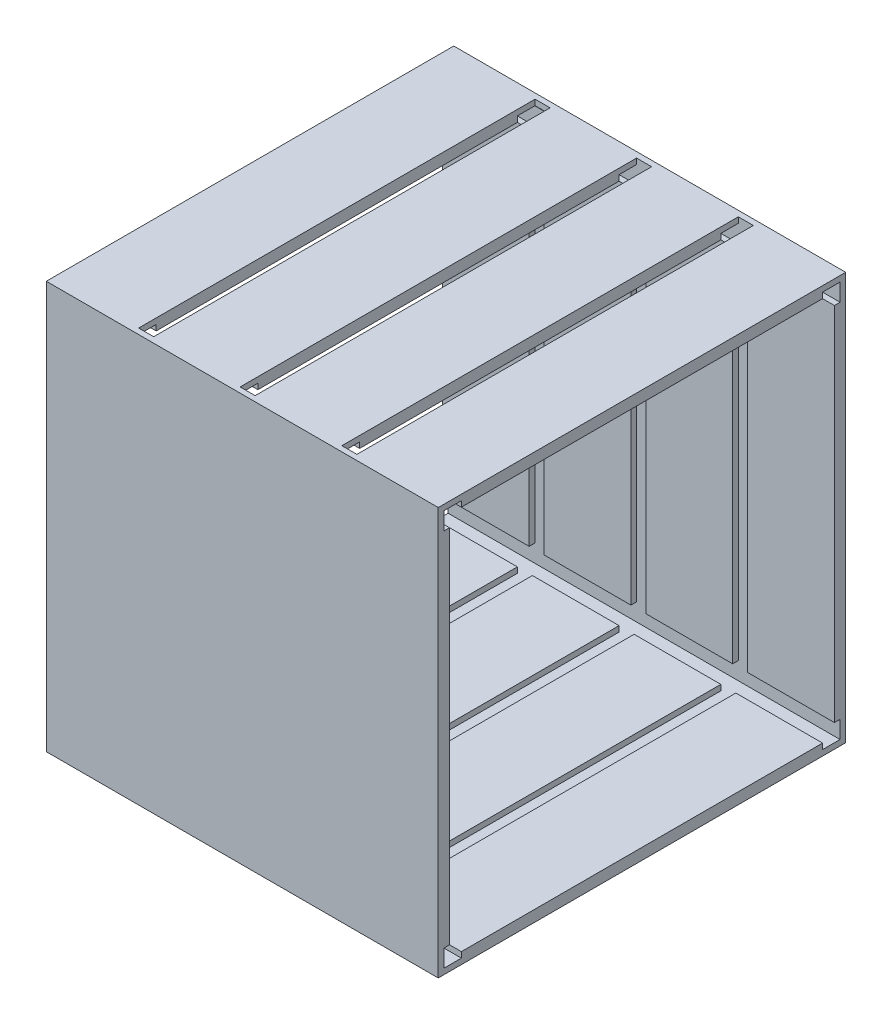
SolidWorks part; units mm, degrees
ref_plane "Front Plane" through (0, 0, 0) normal (0, 0, 1) x (1, 0, 0)
ref_plane "Top Plane" through (0, 0, 0) normal (0, 1, 0) x (1, 0, 0)
ref_plane "Right Plane" through (0, 0, 0) normal (1, 0, 0) x (0, 0, -1)
sketch "Sketch1" plane through (0, 0, 0) normal (1, 0, 0) x (0, 0, -1)
  line L1 (0, 0) -> (688.1, 0)
  line L2 (0, 0) -> (0, 688.1)
  line L3 (0, 688.1) -> (688.1, 688.1)
  line L4 (688.1, 0) -> (688.1, 688.1)
  line L5 (0, 0) -> (19.05, 0) construction
  line L6 (0, 0) -> (0, 19.05) construction
  line L7 (0, 19.05) -> (19.05, 19.05) construction
  line L8 (19.05, 0) -> (19.05, 19.05) construction
  line L9 (19.05, 19.05) -> (669.05, 19.05)
  line L10 (19.05, 19.05) -> (19.05, 669.05)
  line L11 (19.05, 669.05) -> (669.05, 669.05)
  line L12 (669.05, 19.05) -> (669.05, 669.05)
  dimension "D1" = 688.1
  dimension "D2" = 688.1
  dimension "D3" = 19.05
  dimension "D4" = 19.05
  dimension "D5" = 650
  dimension "D6" = 650
extrude "Boss-Extrude1" add sketch "Sketch1" along normal blind 661.9 contours L10 L11 L12 L9 | L2 L3 L4 L1
sketch "Sketch3" plane through (0, 0, -669.05) normal (0, 0, 1) x (1, 0, 0)
  line L1 (0, 669.05) -> (146.425, 669.05) construction
  line L2 (0, 669.05) -> (0, 19.05) construction
  line L3 (0, 19.05) -> (146.425, 19.05) construction
  line L4 (146.425, 669.05) -> (146.425, 19.05) construction
  line L5 (146.425, 669.05) -> (171.825, 669.05)
  line L6 (146.425, 669.05) -> (146.425, 19.05)
  line L7 (146.425, 19.05) -> (171.825, 19.05)
  line L8 (171.825, 669.05) -> (171.825, 19.05)
  line L9 (318.25, 669.05) -> (343.65, 669.05)
  line L10 (318.25, 669.05) -> (318.25, 19.05)
  line L11 (318.25, 19.05) -> (343.65, 19.05)
  line L12 (343.65, 669.05) -> (343.65, 19.05)
  line L13 (490.075, 669.05) -> (515.475, 669.05)
  line L14 (490.075, 669.05) -> (490.075, 19.05)
  line L15 (490.075, 19.05) -> (515.475, 19.05)
  line L16 (515.475, 669.05) -> (515.475, 19.05)
  line L17 (661.9, 688.1) -> (0, 688.1) construction
  point P15 (330.95, 669.05)
  dimension "D1" = 146.425
  dimension "D2" = 650
  dimension "D3" = 25.4
  dimension "D4" = 25.4
  dimension "D5" = 650
  dimension "D6" = 146.425
  dimension "D7" = 25.4
  dimension "D8" = 650
  dimension "D9" = 146.425
  dimension "D10" = 19.05
  dimension "D11" = 19.05
extrude "Cut-Extrude1" cut sketch "Sketch3" against normal blind 9.525
ref_plane "Plane1" through (0, 0, -344.05) normal (0, 0, -1) x (-1, 0, 0)
mirror "Mirror2" about plane through (0, 0, -344.05) normal (0, 0, -1) of "Cut-Extrude1"
ref_plane "Plane2" through (0, 344.05, 0) normal (0, 1, 0) x (1, 0, 0)
sketch "Sketch4" plane through (0, 19.05, 0) normal (0, 1, 0) x (1, 0, 0)
  line L0 (661.9, 688.1) -> (0, 688.1) construction
  line L1 (146.425, 678.575) -> (171.825, 678.575)
  line L2 (146.425, 678.575) -> (146.425, 9.075)
  line L3 (146.425, 9.075) -> (171.825, 9.075)
  line L4 (171.825, 678.575) -> (171.825, 9.075)
  line L5 (0, 0) -> (0, 688.1) construction
  line L6 (661.9, 0) -> (0, 0) construction
  line L7 (318.25, 678.575) -> (343.65, 678.575)
  line L8 (318.25, 678.575) -> (318.25, 9.075)
  line L9 (318.25, 9.075) -> (343.65, 9.075)
  line L10 (343.65, 678.575) -> (343.65, 9.075)
  line L11 (490.075, 678.575) -> (515.475, 678.575)
  line L12 (490.075, 678.575) -> (490.075, 9.525)
  line L13 (490.075, 9.525) -> (515.475, 9.525)
  line L14 (515.475, 678.575) -> (515.475, 9.525)
  dimension "D1" = 25.4
  dimension "D2" = 669.5
  dimension "D3" = 9.525
  dimension "D4" = 146.425
  dimension "D5" = 669.5
  dimension "D6" = 25.4
  dimension "D7" = 9.525
  dimension "D8" = 146.425
  dimension "D9" = 25.4
  dimension "D10" = 146.425
  dimension "D11" = 9.525
  dimension "D12" = 9.525
extrude "Cut-Extrude3" cut sketch "Sketch4" against normal blind 9.525
mirror "Mirror4" about plane through (0, 344.05, 0) normal (0, 1, 0) of "Cut-Extrude3"
sketch "Sketch6" plane through (0, 688.1, 0) normal (0, 1, 0) x (1, 0, 0)
  line L0 (0, 0) -> (0, 688.1) construction
  line L1 (146.425, 679.025) -> (171.825, 679.025)
  line L2 (146.425, 679.025) -> (146.425, 9.525)
  line L3 (146.425, 9.525) -> (171.825, 9.525)
  line L4 (171.825, 679.025) -> (171.825, 9.525)
  line L5 (318.25, 678.575) -> (343.65, 678.575)
  line L6 (318.25, 678.575) -> (318.25, 9.075)
  line L7 (318.25, 9.075) -> (343.65, 9.075)
  line L8 (343.65, 678.575) -> (343.65, 9.075)
  line L9 (490.075, 678.575) -> (515.475, 678.575)
  line L10 (490.075, 678.575) -> (490.075, 9.075)
  line L11 (490.075, 9.075) -> (515.475, 9.075)
  line L12 (515.475, 678.575) -> (515.475, 9.075)
  line L13 (661.9, 0) -> (0, 0) construction
  line L14 (661.9, 688.1) -> (0, 688.1) construction
  dimension "D1" = 669.5
  dimension "D2" = 25.4
  dimension "D3" = 146.425
  dimension "D4" = 9.525
  dimension "D5" = 25.4
  dimension "D6" = 669.5
  dimension "D7" = 9.525
  dimension "D8" = 146.425
  dimension "D9" = 25.4
  dimension "D10" = 669.5
  dimension "D11" = 9.525
  dimension "D12" = 146.425
extrude "Cut-Extrude4" cut sketch "Sketch6" against normal blind 9.525
sketch "Sketch7" plane through (0, 0, 0) normal (-1, 0, 0) x (0, 0, 1)
  line L0 (-19.05, 39.05) -> (-9.525, 39.05)
  line L1 (-19.05, 19.05) -> (-19.05, 669.05) construction
  line L2 (-9.525, 39.05) -> (-9.525, 9.525)
  line L3 (-9.525, 9.525) -> (-39.05, 9.525)
  line L4 (-39.05, 9.525) -> (-39.05, 19.05)
  line L5 (-19.05, 19.05) -> (-669.05, 19.05) construction
  line L6 (-39.05, 19.05) -> (-19.05, 19.05)
  line L7 (-19.05, 19.05) -> (-19.05, 39.05)
  dimension "D1" = 9.525
  dimension "D2" = 20
  dimension "D3" = 20
  dimension "D4" = 9.525
extrude "Cut-Extrude5" cut sketch "Sketch7" against normal blind 700
mirror "Mirror5" about plane through (0, 0, -344.05) normal (0, 0, -1) of "Cut-Extrude5"
mirror "Mirror6" about plane through (0, 344.05, 0) normal (0, 1, 0) of "Mirror5"
